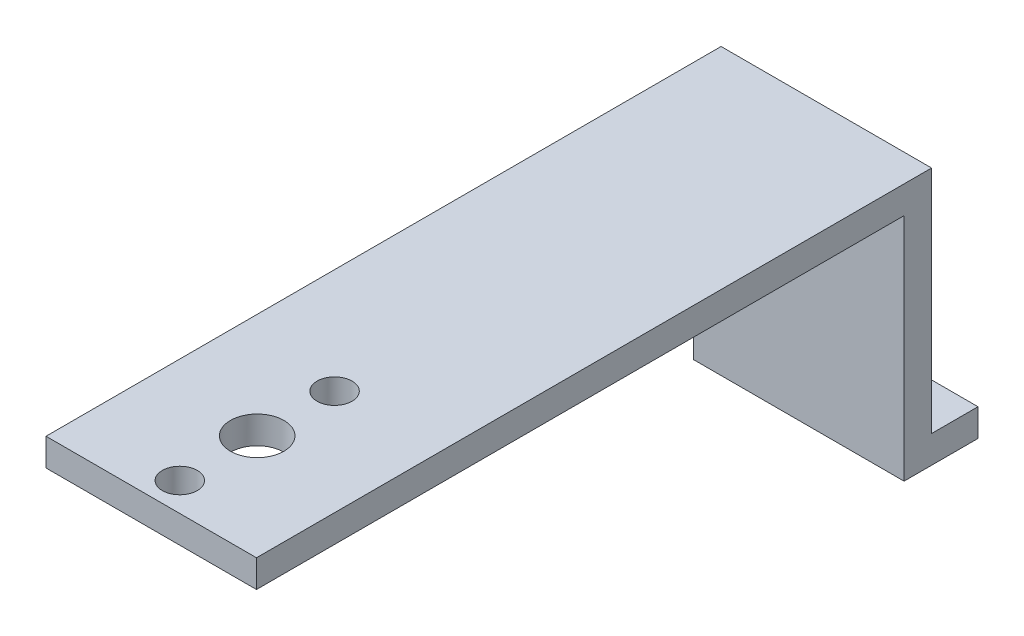
SolidWorks part; units mm, degrees
ref_plane "Front Plane" through (0, 0, 0) normal (0, 0, 1) x (1, 0, 0)
ref_plane "Top Plane" through (0, 0, 0) normal (0, 1, 0) x (1, 0, 0)
ref_plane "Right Plane" through (0, 0, 0) normal (1, 0, 0) x (0, 0, -1)
sketch "Sketch1" plane through (0, 0, 0) normal (1, 0, 0) x (0, 0, -1)
  line L1 (0.889, 3.903) -> (-0.889, 3.903)
  line L2 (0.889, 3.903) -> (0.889, -10.955)
  line L4 (-0.889, 2.125) -> (-0.889, -12.733)
  line L7 (-0.889, 3.903) -> (-42.731, 3.903)
  line L9 (-0.889, 2.125) -> (-42.731, 2.125)
  line L10 (-42.731, 3.903) -> (-42.731, 2.125)
  line L11 (-0.889, -12.733) -> (3.889, -12.733)
  line L13 (0.889, -10.955) -> (3.889, -10.955)
  line L14 (3.889, -12.733) -> (3.889, -10.955)
  point P0 (0, 0)
  dimension "D1" = 1.778
  dimension "D2" = 1.778
  dimension "D3" = 1.778
  dimension "D4" = 13.08
  dimension "D5" = 43.62
  dimension "D6" = 3
extrude "Boss-Extrude1" add sketch "Sketch1" along normal blind 6.8 and the other way blind 6.8
sketch "Sketch2" plane through (0, 3.903, 0) normal (0, 1, 0) x (1, 0, 0)
  circle A0 centre (0, -40.8857) radius 1.1303 construction
  circle A1 centre (0, -35.8857) radius 1.7272 construction
  circle A2 centre (0, -30.8857) radius 1.1303 construction
  circle A3 centre (0, -40.8857) radius 1.1303
  circle A4 centre (0, -35.8857) radius 1.7272
  circle A5 centre (0, -30.8857) radius 1.1303
extrude "Cut-Extrude1" cut sketch "Sketch2" against normal up to next
